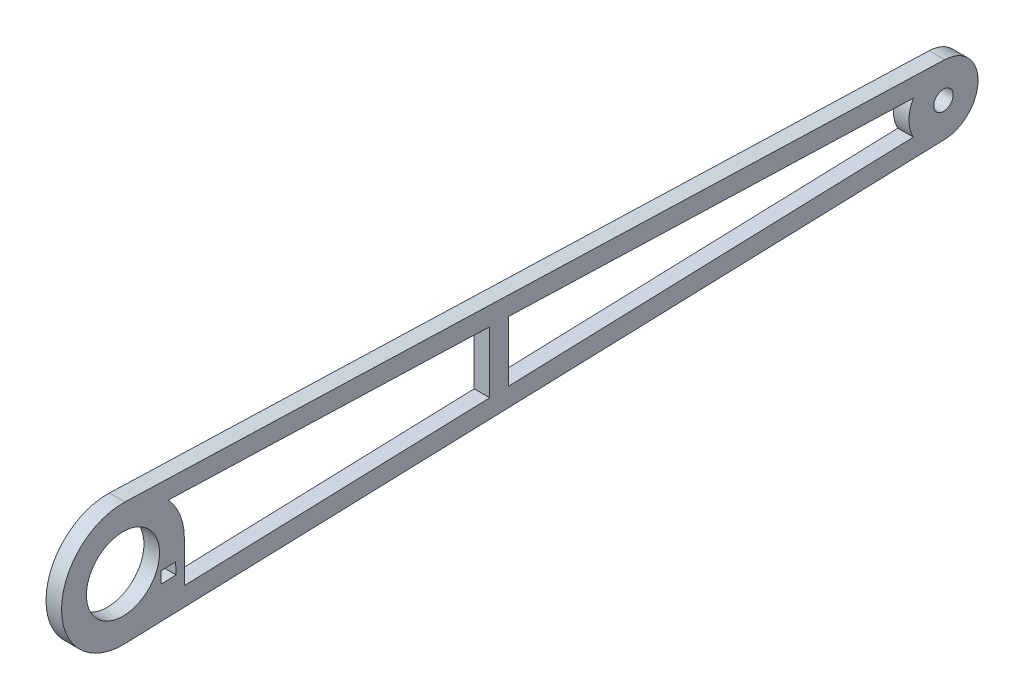
SolidWorks part; units mm, degrees
material "Delrin"
ref_plane "Front Plane" through (0, 0, 0) normal (0, 0, 1) x (1, 0, 0)
ref_plane "Top Plane" through (0, 0, 0) normal (0, 1, 0) x (1, 0, 0)
ref_plane "Right Plane" through (0, 0, 0) normal (1, 0, 0) x (0, 0, -1)
sketch "Sketch1" plane through (0, 0, 0) normal (1, 0, 0) x (0, 0, -1)
  line L0 (0.2053, 6.2704) -> (83.9355, 3.5287)
  line L1 (0, -6.2772) -> (83.9355, -3.5287)
  line L2 (-1000, 0) -> (49000, 0) construction
  line L3 (4.6432, 4.2191) -> (80.7408, 1.7273)
  line L4 (4.6432, -4.2191) -> (80.7408, -1.7273)
  line L5 (0.143, 4.3665) -> (83.8732, 1.6247) construction
  line L6 (-0.0623, -4.3732) -> (83.8732, -1.6247) construction
  line L7 (83.82, -1000) -> (83.82, 49000) construction
  line L8 (5.4651, -2.8302) -> (5.414, -1.5612) construction
  line L9 (5.414, -1.5612) -> (3.8278, -1.6252) construction
  line L10 (3.8789, -2.8941) -> (3.8278, -1.6252) construction
  line L11 (5.4651, -2.8302) -> (3.8789, -2.8941) construction
  line L12 (5.4651, -2.8302) -> (5.414, -1.5612) construction
  line L13 (5.414, -1.5612) -> (3.8278, -1.6252) construction
  line L14 (3.8789, -2.8941) -> (3.8278, -1.6252) construction
  line L15 (5.4651, -2.8302) -> (3.8789, -2.8941) construction
  line L16 (6.2738, 0) -> (6.2738, -4.1657)
  line L17 (39.37, 3.082) -> (39.37, -3.082)
  line L18 (37.465, 3.1444) -> (37.465, -3.1444)
  line L19 (5.3774, -1.6008) -> (3.8674, -1.6617)
  line L20 (3.9154, -2.8545) -> (3.8674, -1.6617)
  line L21 (5.4255, -2.7937) -> (3.9154, -2.8545)
  line L22 (5.4255, -2.7937) -> (5.3774, -1.6008)
  circle A0 centre (0, 0) radius 3.7338
  circle A1 centre (0, 0) radius 6.2738
  circle A2 centre (83.82, 0) radius 0.9906
  circle A3 centre (83.82, 0) radius 3.5306
  circle A4 centre (83.82, 15.875) radius 1.016
  circle A5 centre (83.82, 15.875) radius 3.556
  dimension "D1" = 7.4676
  dimension "D2" = 2.54
  dimension "D3" = 1.9812
  dimension "D8" = 2.032
  dimension "D5" = 83.82
  dimension "D10" = 15.875
  dimension "D11" = 44.45
  dimension "D12" = 1.905
  dimension "D4" = 2.54
  dimension "D6" = 1.905
  dimension "D7" = 1.905
  dimension "D9" = 2.54
  dimension "D13" = 0.0381
extrude "Boss-Extrude1" add sketch "Sketch1" along normal blind 1.5875 contours L2 A1 A0 | A1 L2 A0 | A1 L2 A3 L0 | L2 A1 L1 A3 | L2 A3 A2 | A3 L2 A2 | L3 L18 L4 L17 | A1 L4 L16 region at (0, 3.9454, -42.4708) region at (0, 5.5338, -2.5579) region at (0, 2.3859, -86.2853) region at (0, -3.9454, -42.4708) region at (0, 0, -38.4143) region at (0, -3.173, -5.7993)
sketch3d "3DSketch1"
  line L0 (0, 6.2704, -0.2053) -> (0, 3.5287, -83.9355) construction
  line L1 (0, 3.5649, -82.8294) -> (1.5875, 3.5649, -82.8294)
  line L2 (0, 3.5649, -82.8294) -> (0, -3.5649, -82.8294)
  line L3 (0, -3.5649, -82.8294) -> (1.5875, -3.5649, -82.8294)
  line L4 (1.5875, 3.5649, -82.8294) -> (1.5875, -3.5649, -82.8294)
  line L5 (1.5875, -6.2704, -0.2053) -> (1.5875, -3.5287, -83.9355) construction
